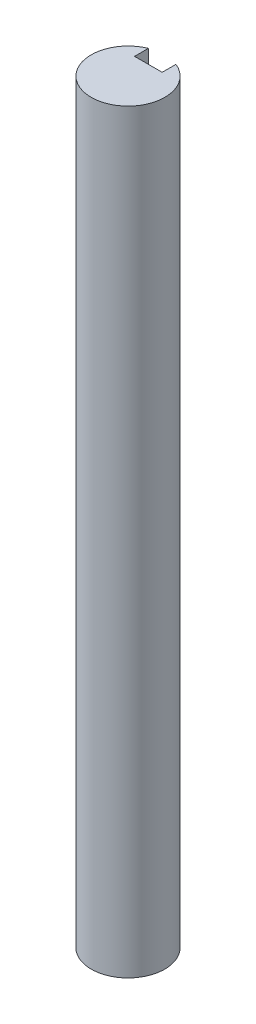
SolidWorks part; units mm, degrees
material "1023 Carbon Steel Sheet (SS)"
ref_plane "Front Plane" through (0, 0, 0) normal (0, 0, 1) x (1, 0, 0)
ref_plane "Top Plane" through (0, 0, 0) normal (0, 1, 0) x (1, 0, 0)
ref_plane "Right Plane" through (0, 0, 0) normal (1, 0, 0) x (0, 0, -1)
sketch "Sketch1" plane through (0, 0, 0) normal (0, 1, 0) x (1, 0, 0)
  line L0 (-1.1906, 2.9433) -> (-1.1906, 1.7527)
  line L1 (-1.1906, 1.7527) -> (1.1906, 1.7527)
  line L2 (1.1906, 1.7527) -> (1.1906, 2.9433)
  arc A0 (-1.1906, 2.9433) -> (1.1906, 2.9433) centre (0, 0) ccw
  point P5 (0, 1.7527)
  dimension "D1" = 6.35
  dimension "D2" = 2.3813
  dimension "D3" = 1.1906
extrude "Boss-Extrude1" add sketch "Sketch1" along normal blind 65.0875
